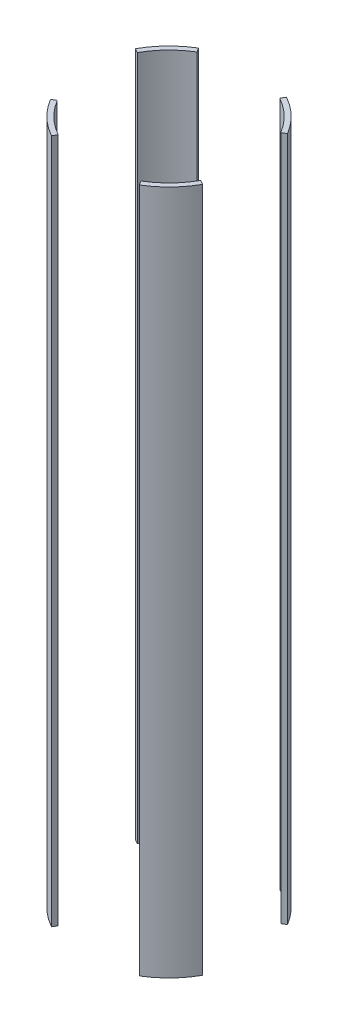
SolidWorks part; units mm, degrees
ref_plane "Front Plane" through (0, 0, 0) normal (0, 0, 1) x (1, 0, 0)
ref_plane "Top Plane" through (0, 0, 0) normal (0, 1, 0) x (1, 0, 0)
ref_plane "Right Plane" through (0, 0, 0) normal (1, 0, 0) x (0, 0, -1)
sketch "Sketch2" plane through (0, 0, 0) normal (0, 1, 0) x (1, 0, 0)
  circle A0 centre (0, 0) radius 88.9
  circle A1 centre (0, 0) radius 83.82
  dimension "D1" = 177.8
  dimension "D2" = 167.64
extrude "Boss-Extrude1" add sketch "Sketch2" along normal mid plane 704.85
sketch "Sketch3" plane through (0, 0, 0) normal (0, 1, 0) x (1, 0, 0)
  line L0 (0, 0) -> (169.6618, 101.6776)
  line L1 (-58.1167, 96.9749) -> (0, 0)
  line L2 (0, 0) -> (53.9, 96.9749)
  line L3 (53.9, 96.9749) -> (-58.1167, 96.9749)
  line L4 (0, 0) -> (70.9917, -118.4586)
  line L5 (70.9917, -118.4586) -> (-65.8409, -118.4586)
  line L6 (-65.8409, -118.4586) -> (0, 0)
  line L7 (169.6618, 101.6776) -> (169.6618, -94.3004)
  line L8 (169.6618, -94.3004) -> (0, 0)
  line L9 (0, 0) -> (-123.7413, 68.7771)
  line L10 (-123.7413, 68.7771) -> (-123.7413, -74.1577)
  line L11 (-123.7413, -74.1577) -> (0, 0)
  dimension "D1" = 60
  dimension "D2" = 60
  dimension "D3" = 60
  dimension "D4" = 60
  dimension "D5" = 30
  dimension "D6" = 30
extrude "Cut-Extrude1" cut sketch "Sketch3" against normal through all both and the other way through all contours L8 L7 L0 | L2 L3 L1 | L10 L11 L9 | L6 L5 L4 region at (-1.4056, 0, -64.65) region at (1.7169, 0, 78.9724) region at (113.1078, 0, -2.4591) region at (-82.4942, 0, 1.7935)
equation "\"D1@Boss-Extrude1\"=3*12"
